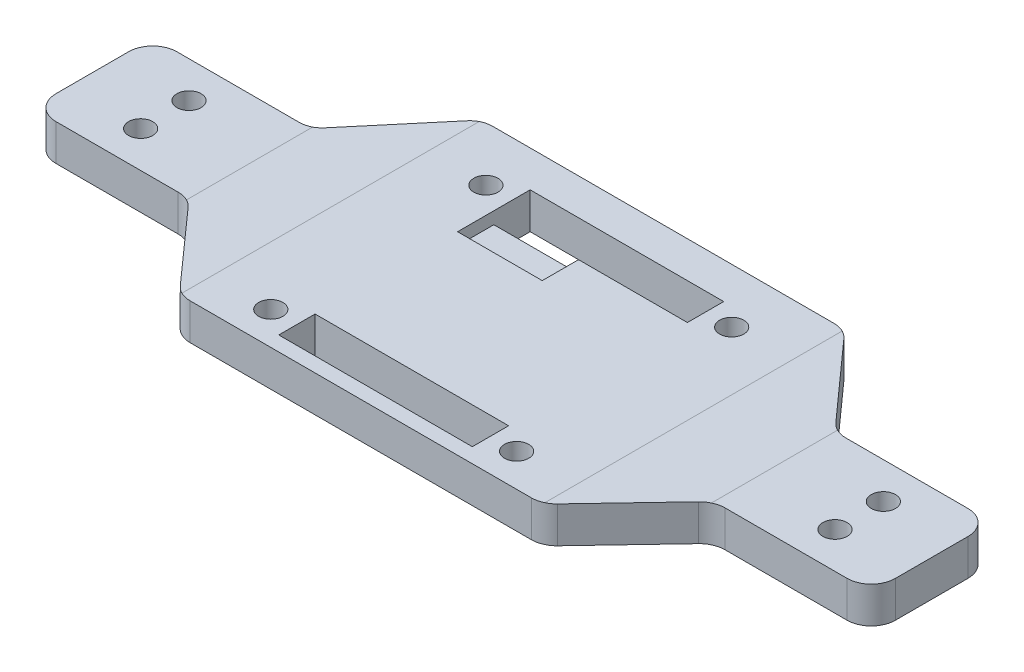
SolidWorks part; units mm, degrees
ref_plane "Front Plane" through (0, 0, 0) normal (0, 0, 1) x (1, 0, 0)
ref_plane "Top Plane" through (0, 0, 0) normal (0, 1, 0) x (1, 0, 0)
ref_plane "Right Plane" through (0, 0, 0) normal (1, 0, 0) x (0, 0, -1)
sketch "Sketch1" plane through (0, 0, 0) normal (0, 1, 0) x (1, 0, 0)
  line L0 (0, -10.0815) -> (0, 10.0815) construction
  line L1 (-34.6981, 5) -> (-24.6981, 5)
  line L2 (-34.6981, 5) -> (-34.6981, -5)
  line L3 (-34.6981, -5) -> (-24.6981, -5)
  line L4 (-24.6981, 5) -> (-24.6981, -5)
  line L5 (-34.6981, 5) -> (-24.6981, -5) construction
  line L6 (-34.6981, -5) -> (-24.6981, 5) construction
  line L7 (-34.6981, 0) -> (-24.6981, 0) construction
  line L8 (-21.6981, -5) -> (-24.6981, -5)
  line L9 (-21.6981, -5) -> (-21.6981, 5)
  line L10 (-21.6981, 5) -> (-24.6981, 5)
  line L11 (-24.6981, -5) -> (-24.6981, 5)
  line L12 (-21.6981, -5) -> (-24.6981, 5) construction
  line L13 (-21.6981, 5) -> (-24.6981, -5) construction
  line L14 (21.6981, 5) -> (24.6981, -5) construction
  line L15 (21.6981, -5) -> (24.6981, 5) construction
  line L16 (34.6981, 0) -> (24.6981, 0) construction
  line L17 (34.6981, -5) -> (24.6981, 5) construction
  line L18 (34.6981, 5) -> (24.6981, -5) construction
  line L19 (24.6981, -5) -> (24.6981, 5)
  line L20 (21.6981, 5) -> (24.6981, 5)
  line L21 (21.6981, -5) -> (21.6981, 5)
  line L22 (21.6981, -5) -> (24.6981, -5)
  line L23 (24.6981, 5) -> (24.6981, -5)
  line L24 (34.6981, -5) -> (24.6981, -5)
  line L25 (34.6981, 5) -> (34.6981, -5)
  line L26 (34.6981, 5) -> (24.6981, 5)
  circle A0 centre (-28.6981, -2) radius 1
  circle A1 centre (-28.6981, 2) radius 1
  circle A2 centre (28.6981, 2) radius 1
  circle A3 centre (28.6981, -2) radius 1
  point P0 (-29.6981, 0)
  point P5 (-23.1981, 0)
  point P10 (0, 0)
  point P30 (23.1981, 0)
  point P31 (29.6981, 0)
  dimension "D2" = 3
  dimension "D3" = 4
  dimension "D1" = 28.6981
extrude "Boss-Extrude1" add sketch "Sketch1" along normal blind 3 contours L4 L1 L2 L3 A0 A1 | L9 L10 L4 L8 | L21 L22 L19 L20 | L25 L26 L19 L24 A2 A3 region at (-29.7651, 0, 0) region at (-23.1981, 0, 0) region at (23.1981, 0, 0) region at (29.7651, 0, 0)
ref_plane "Plane2" through (0, 3.215, 0) normal (0, 1, 0) x (1, 0, 0)
sketch "Sketch3" plane through (0, 3.215, 0) normal (0, 1, 0) x (1, 0, 0)
  line L0 (21.6981, 5) -> (21.6981, -5) construction
  line L1 (21.6981, -5) -> (34.6981, -5) construction
  line L2 (34.6981, -5) -> (34.6981, 5) construction
  line L3 (34.6981, 5) -> (21.6981, 5) construction
  line L4 (-34.6981, -5) -> (-21.6981, -5) construction
  line L5 (-21.6981, -5) -> (-21.6981, 5) construction
  line L6 (-21.6981, 5) -> (-34.6981, 5) construction
  line L7 (-34.6981, 5) -> (-34.6981, -5) construction
  line L8 (21.6981, 5) -> (21.6981, -5)
  line L9 (21.6981, -5) -> (34.6981, -5)
  line L10 (34.6981, -5) -> (34.6981, 5)
  line L11 (34.6981, 5) -> (21.6981, 5)
  line L12 (-34.6981, -5) -> (-21.6981, -5)
  line L13 (-21.6981, -5) -> (-21.6981, 5)
  line L14 (-21.6981, 5) -> (-34.6981, 5)
  line L15 (-34.6981, 5) -> (-34.6981, -5)
  line L16 (-36.8996, 0) -> (36.9117, 0) construction
  line L17 (0, 16.1382) -> (0, -11.6022) construction
  line L19 (-14.994, -12.5) -> (15.006, -12.5)
  line L20 (-14.994, -12.5) -> (-14.994, 12.5)
  line L21 (-14.994, 12.5) -> (15.006, 12.5)
  line L22 (15.006, -12.5) -> (15.006, 12.5)
  line L23 (-14.994, -12.5) -> (15.006, 12.5) construction
  line L24 (-14.994, 12.5) -> (15.006, -12.5) construction
  point P13 (0.006, 0)
extrude "Boss-Extrude2" add sketch "Sketch3" against normal blind 3 separate body contours L19 L22 L21 L20 region at (0.006, 3.215, 0)
loft "Loft2" add section face at (-21.6981, 1.5, 0) section face at (-14.994, 1.715, 0) connector at (-21.6981, 3, 5) connector at (-14.994, 3.215, 12.5)
loft "Loft3" add section face at (15.006, 1.715, 0) section face at (21.6981, 1.5, 0) connector at (15.006, 3.215, 12.5) connector at (21.6981, 3, 5)
sketch "Sketch4" plane through (0, 3.215, 0) normal (0, 1, 0) x (1, 0, 0)
  line L0 (-37.4472, 0) -> (41.667, 0) construction
  line L1 (0, 18.5225) -> (0, -15.3071) construction
  line L2 (-11.9434, -0.89) -> (12.6797, -0.89) construction
  line L3 (-8, 9.5) -> (8, 9.5)
  line L4 (-8, 9.5) -> (-8, 6.5)
  line L5 (-8, 6.5) -> (8, 6.5)
  line L6 (8, 9.5) -> (8, 6.5)
  line L7 (-8, 9.5) -> (8, 6.5) construction
  line L8 (-8, 6.5) -> (8, 9.5) construction
  line L9 (-8, -8.28) -> (8, -8.28)
  line L10 (8, -11.28) -> (8, -8.28)
  line L11 (-8, -11.28) -> (8, -11.28)
  line L12 (-8, -11.28) -> (-8, -8.28)
  circle A0 centre (10.16, 8) radius 1
  circle A1 centre (-10.16, 8) radius 1
  circle A2 centre (10.16, -9.78) radius 1
  circle A3 centre (-10.16, -9.78) radius 1
  point P5 (0, 8)
  dimension "D1" = 8
  dimension "D2" = 10.16
  dimension "D3" = 8.89
extrude "Cut-Extrude1" cut sketch "Sketch4" against normal through all
sketch "Sketch5" plane through (0, 3.215, 0) normal (0, 1, 0) x (1, 0, 0)
  line L0 (-10, 0) -> (10, 0) construction
  text T0 "BNO085"
  point P5 (0, 0)
fillet "Fillet1" radius 2 12 edges at (21.6981, 1.5, -5) (34.6981, 1.5, -5) (34.6981, 1.5, 5) (21.6981, 1.5, 5) (-21.6981, 1.5, 5) (-34.6981, 1.5, 5) (-34.6981, 1.5, -5) (-21.6981, 1.5, -5)
sketch "Sketch6" plane through (0, 3.215, 0) normal (0, 1, 0) x (1, 0, 0)
  line L0 (-8, 6.5) -> (-8, 3.5)
  line L1 (-8, 3.5) -> (-1, 3.5)
  line L2 (-1, 3.5) -> (-1, 6.5)
  line L3 (-8, 6.5) -> (8, 6.5) construction
  line L4 (-8, 6.5) -> (-1, 6.5)
extrude "Cut-Extrude2" cut sketch "Sketch6" against normal blind 1
